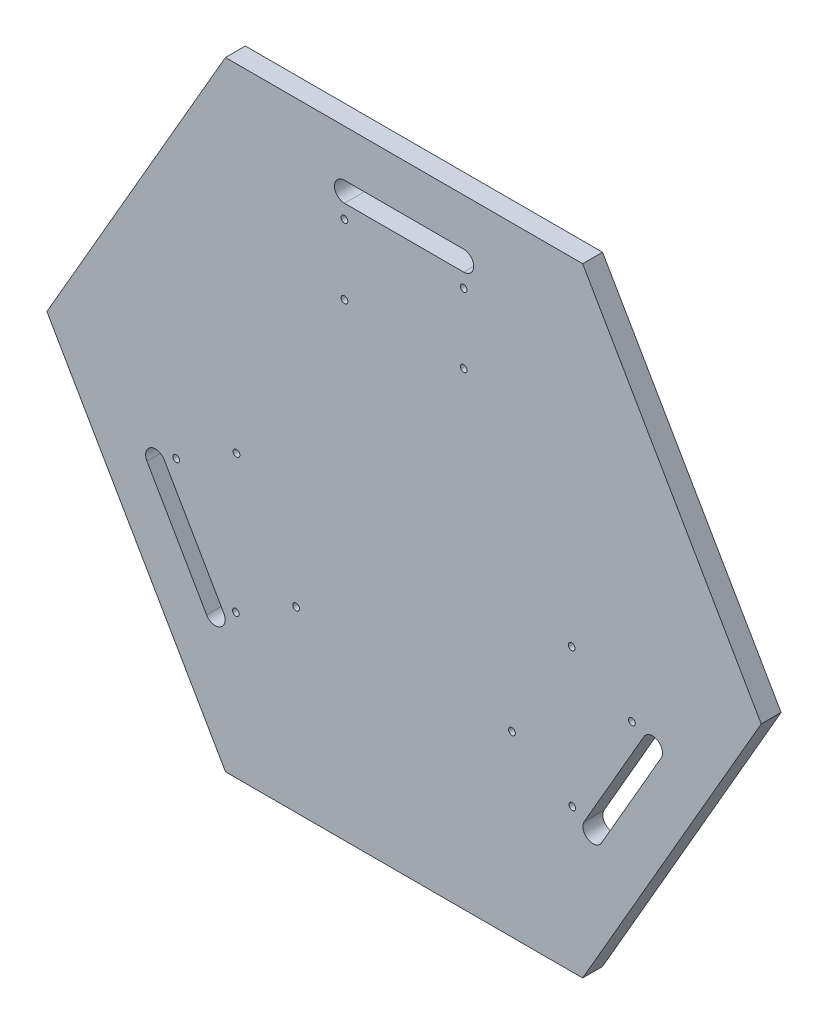
SolidWorks part; units mm, degrees
note: '?' marks a value the reader was unsure of.
material "Maple"
ref_plane "Front Plane" through (0, 0, 0) normal (0, 0, 1) x (1, 0, 0)
ref_plane "Top Plane" through (0, 0, 0) normal (0, 1, 0) x (1, 0, 0)
ref_plane "Right Plane" through (0, 0, 0) normal (1, 0, 0) x (0, 0, -1)
other "STL Graphics1"
sketch "Sketch1" plane through (0, 0, 0) normal (0, 0, 1) x (1, 0, 0)
  line L0 (0, -1000) -> (0, 49000) construction
  point P0 (30, 80)
  point P2 (30, 115)
  point P5 (-30, 80)
  point P6 (-30, 115)
  point P10 (54.282, -65.9808)
  point P11 (84.5929, -83.4808)
  point P12 (84.282, -14.0192)
  point P13 (114.5929, -31.5192)
  point P14 (-84.282, -14.0192)
  point P15 (-114.5929, -31.5192)
  point P16 (-54.282, -65.9808)
  point P17 (-84.5929, -83.4808)
  point P18 (0, 0)
  dimension "D4" = 3
sketch "Sketch2" plane through (0, 0, 0) normal (0, 0, 1) x (1, 0, 0)
  line L1 (-89.8213, 155.575) -> (-179.6425, 0)
  line L2 (-179.6425, 0) -> (-89.8213, -155.575)
  line L3 (-89.8213, -155.575) -> (89.8213, -155.575)
  line L4 (89.8213, -155.575) -> (179.6425, 0)
  line L5 (179.6425, 0) -> (89.8213, 155.575)
  line L6 (89.8213, 155.575) -> (-89.8213, 155.575)
  circle A0 centre (0, 0) radius 155.575 construction
  dimension "D1" = 311.15
extrude "Boss-Extrude1" add sketch "Sketch2" along normal mid plane 10
sketch "Sketch3" plane through (0, 0, 5) normal (0, 0, 1) x (1, 0, 0)
  line L0 (-30, 127) -> (30, 127) construction
  line L1 (0, -201000) -> (0, 249000) construction
  line L2 (-30, 132) -> (30, 132)
  line L3 (-30, 122) -> (30, 122)
  arc A0 (-30, 132) -> (-30, 122) centre (-30, 127) ccw
  arc A1 (30, 122) -> (30, 132) centre (30, 127) ccw
  point P4 (0, 127)
  dimension "D2" = 5
  dimension "D1" = 127
  dimension "D3" = 60
extrude "Cut-Extrude1" cut sketch "Sketch3" against normal through all
hole_wizard "M3 Clearance Hole1" positions "Sketch5" profile "Sketch4" hole size "M3" standard "ANSI Metric" end condition through all
sketch "Sketch5" plane through (0, 0, 5) normal (0, 0, 1) x (1, 0, 0)
  point P0 (-30, 115)
  point P3 (30, 115)
  point P6 (-30, 80)
  point P9 (30, 80)
sketch "Sketch4" plane through (-30, 115, 5) normal (1, 0, 0) x (0, -1, 0)
  line L0 (0, 0) -> (0, 10)
  line L1 (0, 10) -> (1.7, 10)
  line L2 (1.7, 10) -> (1.7, 0)
  line L5 (1.7, 0) -> (0, 0)
  line L11 (0, -6.35) -> (0, 107.95) construction
  dimension "Thru Hole Dia." = 3.4
  dimension "Thru Hole Depth" = 10
ref_axis "Major-axis" through (0, 0, -20.25) along (0, 0, 1)?
pattern_circular "CirPattern1" count 3 over 360 about axis through (0, 0, 0) along (0, 0, 1) of "Cut-Extrude1", "M3 Clearance Hole1"
